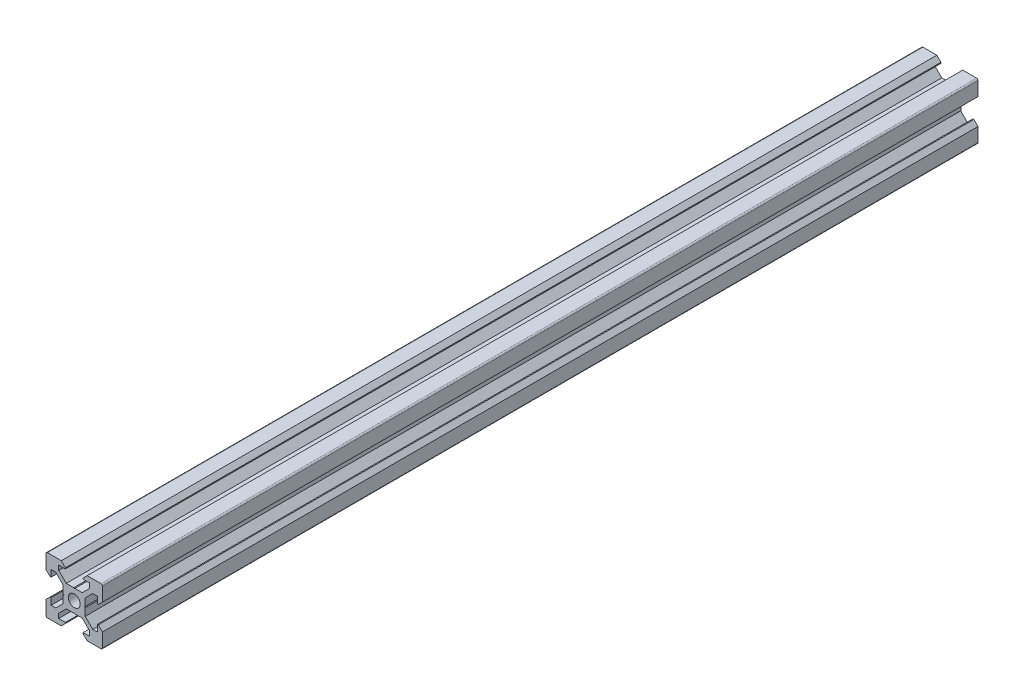
SolidWorks part; units mm, degrees
material "6061-T6 (SS)"
ref_plane "Front Plane" through (0, 0, 0) normal (0, 0, 1) x (1, 0, 0)
ref_plane "Top Plane" through (0, 0, 0) normal (0, 1, 0) x (1, 0, 0)
ref_plane "Right Plane" through (0, 0, 0) normal (1, 0, 0) x (0, 0, -1)
sketch "Sketch1" plane through (0, 0, 0) normal (0, 0, 1) x (1, 0, 0)
  line L1 (9.5, -10) -> (-9.5, -10)
  line L2 (10, -9.5) -> (10, 9.5)
  line L3 (9.5, 10) -> (-9.5, 10)
  line L4 (-10, -9.5) -> (-10, 9.5)
  line L5 (10, -10) -> (-10, 10) construction
  line L6 (10, 10) -> (-10, -10) construction
  circle A0 centre (0, 0) radius 2.1
  arc A1 (-9.5, 10) -> (-10, 9.5) centre (-9.5, 9.5) ccw
  arc A2 (10, 9.5) -> (9.5, 10) centre (9.5, 9.5) ccw
  arc A3 (9.5, -10) -> (10, -9.5) centre (9.5, -9.5) ccw
  arc A4 (-9.5, -10) -> (-10, -9.5) centre (-9.5, -9.5) cw
  point P0 (0, 0)
  line B0 (0, 0) -> (0, 10) construction
  line B1 (0, 3.69) -> (-0.21, 3.9)
  line B2 (-0.21, 3.9) -> (-2.8393, 3.9)
  line B3 (-2.8393, 3.9) -> (-5.5, 6.5607)
  line B4 (-5.5, 6.5607) -> (-5.5, 8.2)
  line B5 (-5.5, 8.2) -> (-3.125, 8.2)
  line B6 (-3.125, 8.2) -> (-3.125, 8.545)
  line B7 (-3.125, 8.545) -> (-4.58, 10)
  line B8 (-4.58, 10) -> (4.58, 10)
  line B9 (0, 0) -> (-5.9132, 5.9132) construction
  line B10 (3.125, 8.545) -> (4.58, 10)
  line B11 (3.125, 8.2) -> (3.125, 8.545)
  line B12 (5.5, 8.2) -> (3.125, 8.2)
  line B13 (5.5, 6.5607) -> (5.5, 8.2)
  line B14 (2.8393, 3.9) -> (5.5, 6.5607)
  line B15 (0.21, 3.9) -> (2.8393, 3.9)
  line B16 (0, 3.69) -> (0.21, 3.9)
  line B17 (0, 0) -> (-10, 0) construction
  line B18 (-3.69, 0) -> (-3.9, -0.21)
  line B19 (-3.9, -0.21) -> (-3.9, -2.8393)
  line B20 (-3.9, -2.8393) -> (-6.5607, -5.5)
  line B21 (-6.5607, -5.5) -> (-8.2, -5.5)
  line B22 (-8.2, -5.5) -> (-8.2, -3.125)
  line B23 (-8.2, -3.125) -> (-8.545, -3.125)
  line B24 (-8.545, -3.125) -> (-10, -4.58)
  line B25 (-10, -4.58) -> (-10, 4.58)
  line B26 (0, 0) -> (-5.9132, -5.9132) construction
  line B27 (-8.545, 3.125) -> (-10, 4.58)
  line B28 (-8.2, 3.125) -> (-8.545, 3.125)
  line B29 (-8.2, 5.5) -> (-8.2, 3.125)
  line B30 (-6.5607, 5.5) -> (-8.2, 5.5)
  line B31 (-3.9, 2.8393) -> (-6.5607, 5.5)
  line B32 (-3.9, 0.21) -> (-3.9, 2.8393)
  line B33 (-3.69, 0) -> (-3.9, 0.21)
  line B34 (0, 0) -> (0, -10) construction
  line B35 (0, -3.69) -> (0.21, -3.9)
  line B36 (0.21, -3.9) -> (2.8393, -3.9)
  line B37 (2.8393, -3.9) -> (5.5, -6.5607)
  line B38 (5.5, -6.5607) -> (5.5, -8.2)
  line B39 (5.5, -8.2) -> (3.125, -8.2)
  line B40 (3.125, -8.2) -> (3.125, -8.545)
  line B41 (3.125, -8.545) -> (4.58, -10)
  line B42 (4.58, -10) -> (-4.58, -10)
  line B43 (0, 0) -> (5.9132, -5.9132) construction
  line B44 (-3.125, -8.545) -> (-4.58, -10)
  line B45 (-3.125, -8.2) -> (-3.125, -8.545)
  line B46 (-5.5, -8.2) -> (-3.125, -8.2)
  line B47 (-5.5, -6.5607) -> (-5.5, -8.2)
  line B48 (-2.8393, -3.9) -> (-5.5, -6.5607)
  line B49 (-0.21, -3.9) -> (-2.8393, -3.9)
  line B50 (0, -3.69) -> (-0.21, -3.9)
  line B51 (0, 0) -> (10, 0) construction
  line B52 (3.69, 0) -> (3.9, 0.21)
  line B53 (3.9, 0.21) -> (3.9, 2.8393)
  line B54 (3.9, 2.8393) -> (6.5607, 5.5)
  line B55 (6.5607, 5.5) -> (8.2, 5.5)
  line B56 (8.2, 5.5) -> (8.2, 3.125)
  line B57 (8.2, 3.125) -> (8.545, 3.125)
  line B58 (8.545, 3.125) -> (10, 4.58)
  line B59 (10, 4.58) -> (10, -4.58)
  line B60 (0, 0) -> (5.9132, 5.9132) construction
  line B61 (8.545, -3.125) -> (10, -4.58)
  line B62 (8.2, -3.125) -> (8.545, -3.125)
  line B63 (8.2, -5.5) -> (8.2, -3.125)
  line B64 (6.5607, -5.5) -> (8.2, -5.5)
  line B65 (3.9, -2.8393) -> (6.5607, -5.5)
  line B66 (3.9, -0.21) -> (3.9, -2.8393)
  line B67 (3.69, 0) -> (3.9, -0.21)
  dimension "D1" = 4.2
  dimension "D3" = 0.5
  dimension "D2" = 20
sketch_block_instance "V Slot 1-4"
sketch_block "V Slot 1" parameters "D1"=10, "D2"=11, "D3"=4.3, "D4"=1.8, "D5"=0.21, "D6"=45, "D7"=9.16, "D8"=1.5, "D9"=6.25
sketch_block_instance "V Slot 1-5"
sketch_block_instance "V Slot 1-6"
sketch_block_instance "V Slot 1-7"
extrude "Boss-Extrude1" add sketch "Sketch1" along normal blind 500 contours B67 B52 B53 B54 B55 B56 B57 B58 L2 A2 L3 B10 B11 B12 B13 B14 B15 B16 B1 B2 B3 B4 B5 B6 B7 A1 L4 B27 B28 B29 B30 B31 B32 B33 B18 B19 B20 B21 B22 B23 B24 A4 L1 B44 B45 B46 B47 B48 B49 region at (7.04, -9.7172, 0)
sketch "Sketch2" plane through (0, 0, 500) normal (0, 0, 1) x (1, 0, 0)
  line L1 (-28.5697, 18.4094) -> (25.7732, 18.4094)
  line L2 (-28.5697, 18.4094) -> (-28.5697, -27.0318)
  line L3 (-28.5697, -27.0318) -> (25.7732, -27.0318)
  line L4 (25.7732, 18.4094) -> (25.7732, -27.0318)
extrude "Cut-Extrude1" cut sketch "Sketch2" against normal blind 189.7888
